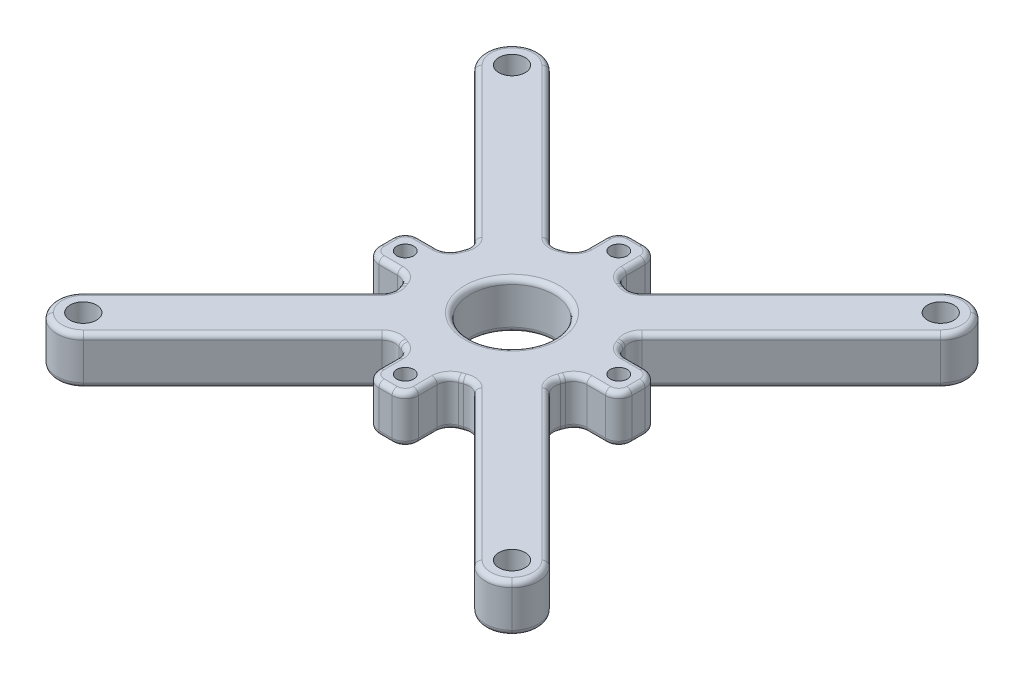
SolidWorks part; units mm, degrees
ref_plane "Front Plane" through (0, 0, 0) normal (0, 0, 1) x (1, 0, 0)
ref_plane "Top Plane" through (0, 0, 0) normal (0, 1, 0) x (1, 0, 0)
ref_plane "Right Plane" through (0, 0, 0) normal (1, 0, 0) x (0, 0, -1)
sketch "Geometry" plane through (0, 0, 0) normal (0, 1, 0) x (1, 0, 0)
  line L2 (-55, 0) -> (55, 0) construction
  line L3 (-24, -3.75) -> (24, -3.75) construction
  line L4 (-24, -3.75) -> (-24, 3.75) construction
  line L5 (-24, 3.75) -> (24, 3.75) construction
  line L6 (24, -3.75) -> (24, 3.75) construction
  line L7 (-24, -3.75) -> (24, 3.75) construction
  line L8 (-24, 3.75) -> (24, -3.75) construction
  line L9 (-3.75, -24) -> (3.75, -24) construction
  line L10 (-3.75, -24) -> (-3.75, 24) construction
  line L11 (-3.75, 24) -> (3.75, 24) construction
  line L12 (3.75, -24) -> (3.75, 24) construction
  line L13 (-3.75, -24) -> (3.75, 24) construction
  line L14 (-3.75, 24) -> (3.75, -24) construction
  line L15 (-16.0682, 3.75) -> (-24, 3.75)
  line L16 (-24, 3.75) -> (-24, -3.75)
  line L17 (-24, -3.75) -> (-16.0682, -3.75)
  line L18 (3.75, 16.0682) -> (3.75, 24)
  line L19 (3.75, 24) -> (-3.75, 24)
  line L20 (-3.75, 24) -> (-3.75, 16.0682)
  line L21 (16.0682, -3.75) -> (24, -3.75)
  line L22 (24, -3.75) -> (24, 3.75)
  line L23 (24, 3.75) -> (16.0682, 3.75)
  line L24 (-3.75, -16.0682) -> (-3.75, -24)
  line L25 (-3.75, -24) -> (3.75, -24)
  line L26 (3.75, -24) -> (3.75, -16.0682)
  circle A0 centre (0, 0) radius 7.9375
  circle A1 centre (0, 0) radius 16.5
  circle A2 centre (-20.25, 0) radius 1.6
  circle A3 centre (0, 20.25) radius 1.6
  circle A4 centre (20.25, 0) radius 1.6
  circle A5 centre (0, -20.25) radius 1.6
  circle A6 centre (-20.25, 0) radius 2.75
  circle A7 centre (0, 20.25) radius 2.75
  circle A8 centre (20.25, 0) radius 2.75
  circle A9 centre (0, -20.25) radius 2.75
  dimension "D1" = 15.875
  dimension "D2" = 33
  dimension "D6" = 3.2
  dimension "D8" = 5.5
  dimension "D3" = 7.5
  dimension "D4" = 24
  dimension "D5" = 3.75
  dimension "D7" = 4
  dimension "D9" = 4
  dimension "D10" = 4
extrude "Cap and Holes" add sketch "Geometry" along normal blind 9 contours A1 A0 | A1 L15 L16 L17 A6 | A1 L24 L25 L26 A9 | A1 L21 L22 L23 A8 | A1 L18 L19 L20 A7 | A7 A3 | A6 A2 | A9 A5 | A8 A4 region at (-16.6092, 0, 0) region at (-11.3373, 0, -11.3373) region at (-3.6408, 0, -20.0341) region at (0, 0, 16.6092) region at (20.0341, 0, -3.6408) region at (-22.9222, 0, 0) region at (-2.6722, 0, -20.25) region at (17.5778, 0, 0) region at (-2.6722, 0, 20.25)
extrude "Socket_Head" cut sketch "Sketch1<3>" along normal blind 3 contours A9 A5 | A8 A4 | A7 A3 | A6 A2 region at (-22.9222, 0, 0) region at (-2.6722, 0, -20.25) region at (17.5778, 0, 0) region at (-2.6722, 0, 20.25)
sketch "Sketch1<3>" plane through (0, 0, 0) normal (0, 1, 0) x (1, 0, 0) same geometry as "Geometry"
sketch "Sketch1" plane through (0, 9, 0) normal (0, 1, 0) x (1, 0, 0)
  line L0 (-47.7297, 40.6586) -> (40.6586, -47.7297)
  line L1 (40.6586, -47.7297) -> (47.7297, -40.6586)
  line L2 (47.7297, -40.6586) -> (-40.6586, 47.7297)
  line L3 (-40.6586, 47.7297) -> (-47.7297, 40.6586)
  line L4 (-44.1942, 44.1942) -> (44.1942, -44.1942) construction
  line L5 (-4.95, 0) -> (4.95, 0) construction
  line L6 (3.5355, 3.5355) -> (-3.5355, -3.5355) construction
  line L7 (0, -24) -> (0, 24) construction
  line L8 (3.75, 24) -> (-3.75, 24) construction
  line L9 (-47.7297, -40.6586) -> (40.6586, 47.7297)
  line L10 (-40.6586, -47.7297) -> (-47.7297, -40.6586)
  line L11 (47.7297, 40.6586) -> (-40.6586, -47.7297)
  line L12 (40.6586, 47.7297) -> (47.7297, 40.6586)
  line L13 (-44.1942, 37.1231) -> (-37.1231, 44.1942) construction
  circle A0 centre (-40.6586, 40.6586) radius 2.5
  circle A1 centre (40.6586, -40.6586) radius 2.5
  circle A2 centre (40.6586, 40.6586) radius 2.5
  circle A3 centre (-40.6586, -40.6586) radius 2.5
  point P10 (0, 0)
  point P11 (0, 0)
  point P14 (0, 0)
  point P20 (0, 0)
  point P29 (-40.6586, 40.6586)
  circle M15 centre (0, 0) radius 7.9375
  arc M16 (3.75, -16.0682) -> (16.0682, -3.75) centre (0, 0) ccw
  arc M20 (16.0682, 3.75) -> (3.75, 16.0682) centre (0, 0) ccw
  arc M24 (-3.75, 16.0682) -> (-16.0682, 3.75) centre (0, 0) ccw
  arc M28 (-16.0682, -3.75) -> (-3.75, -16.0682) centre (0, 0) ccw
  dimension "D4" = 5
  dimension "D1" = 45
  dimension "D2" = 125
  dimension "D3" = 10
  dimension "D5" = 5
extrude "Boss-Extrude1" add sketch "Sketch1" against normal up to surface (9 mm away) contours L2 L3 L0 A0 M24 | L12 L9 L11 A2 M20 | L1 L2 L0 A1 M16 | L11 L9 L10 A3 M28 | L2 L0 M15 M24 | L11 L9 M20 M15 | L2 L0 M16 M15 | L11 L9 M15 M28 region at (-27.2715, 9, -27.2715) region at (-8.3422, 9, -8.3422) region at (-8.3422, 9, 8.3422) region at (8.3422, 9, -8.3422) region at (-27.2715, 9, 27.2715) region at (8.3422, 9, 8.3422) region at (27.2715, 9, -27.2715) region at (27.2715, 9, 27.2715) up to face at (0, 0, 23)
fillet "Fillet1" radius 2.5 16 edges at (-16.0682, 4.5, -3.75) (-14.6542, 4.5, -7.5831) (-7.5831, 4.5, -14.6542) (-3.75, 4.5, -16.0682) (3.75, 4.5, -16.0682) (7.5831, 4.5, -14.6542) (16.0682, 4.5, -3.75) (14.6542, 4.5, -7.5831) (14.6542, 4.5, 7.5831) (16.0682, 4.5, 3.75) (3.75, 4.5, 16.0682) (7.5831, 4.5, 14.6542) (-3.75, 4.5, 16.0682) (-7.5831, 4.5, 14.6542) (-14.6542, 4.5, 7.5831) (-16.0682, 4.5, 3.75)
fillet "Fillet2" radius 2.5 8 edges at (-24, 4.5, 3.75) (-24, 4.5, -3.75) (-3.75, 4.5, -24) (3.75, 4.5, -24) (24, 4.5, -3.75) (24, 4.5, 3.75) (3.75, 4.5, 24) (-3.75, 4.5, 24)
fillet "Fillet3" radius 5 8 edges at (47.7297, 4.5, -40.6586) (40.6586, 4.5, -47.7297) (-40.6586, 4.5, -47.7297) (-47.7297, 4.5, -40.6586) (-47.7297, 4.5, 40.6586) (-40.6586, 4.5, 47.7297) (47.7297, 4.5, 40.6586) (40.6586, 4.5, 47.7297)
fillet "Fillet4" radius 1 120 edges at (-15.1986, 0, 7.5445) (-15.4573, 0, 5.7724) (-16.4945, 0, 4.2121) (-19.7213, 0, 3.75) (-23.2678, 0, 3.0178) (-24, 0, 0) (-23.2678, 0, -3.0178) (-19.7213, 0, -3.75) (-16.4945, 0, -4.2121) (-15.4573, 0, -5.7724) (-15.1986, 0, -7.5445) (-30.0369, 0, -22.9658) (-45.6586, 0, -40.6586) (-40.6586, 0, -45.6586) (-22.9658, 0, -30.0369) (-7.5445, 0, -15.1986) (-5.7724, 0, -15.4573) (-4.2121, 0, -16.4945) (-3.75, 0, -19.7213) (-3.0178, 0, -23.2678) (0, 0, -24) (3.0178, 0, -23.2678) (3.75, 0, -19.7213) (4.2121, 0, -16.4945) (5.7724, 0, -15.4573) (7.5445, 0, -15.1986) (22.9658, 0, -30.0369) (40.6586, 0, -45.6586) (45.6586, 0, -40.6586) (30.0369, 0, -22.9658) (15.1986, 0, -7.5445) (15.4573, 0, -5.7724) (16.4945, 0, -4.2121) (19.7213, 0, -3.75) (23.2678, 0, -3.0178) (24, 0, 0) (23.2678, 0, 3.0178) (19.7213, 0, 3.75) (16.4945, 0, 4.2121) (15.4573, 0, 5.7724) (15.1986, 0, 7.5445) (30.0369, 0, 22.9658) (45.6586, 0, 40.6586) (40.6586, 0, 45.6586) (22.9658, 0, 30.0369) (7.5445, 0, 15.1986) (5.7724, 0, 15.4573) (4.2121, 0, 16.4945) (3.75, 0, 19.7213) (3.0178, 0, 23.2678) (0, 0, 24) (-3.0178, 0, 23.2678) (-3.75, 0, 19.7213) (-4.2121, 0, 16.4945) (-5.7724, 0, 15.4573) (-7.5445, 0, 15.1986) (-22.9658, 0, 30.0369) (-40.6586, 0, 45.6586) (-45.6586, 0, 40.6586) (7.5445, 9, -15.1986) (5.7724, 9, -15.4573) (4.2121, 9, -16.4945) (3.75, 9, -19.7213) (3.0178, 9, -23.2678) (0, 9, -24) (-3.0178, 9, -23.2678) (-3.75, 9, -19.7213) (-4.2121, 9, -16.4945) (-5.7724, 9, -15.4573) (-7.5445, 9, -15.1986) (-22.9658, 9, -30.0369) (-40.6586, 9, -45.6586) (-45.6586, 9, -40.6586) (-30.0369, 9, -22.9658) (-15.1986, 9, -7.5445) (-15.4573, 9, -5.7724) (-16.4945, 9, -4.2121) (-19.7213, 9, -3.75) (-23.2678, 9, -3.0178) (-24, 9, 0) (-23.2678, 9, 3.0178) (-19.7213, 9, 3.75) (-16.4945, 9, 4.2121) (-15.4573, 9, 5.7724) (-15.1986, 9, 7.5445) (-30.0369, 9, 22.9658) (-45.6586, 9, 40.6586) (-40.6586, 9, 45.6586) (-22.9658, 9, 30.0369) (-7.5445, 9, 15.1986) (-5.7724, 9, 15.4573) (-4.2121, 9, 16.4945) (-3.75, 9, 19.7213) (-3.0178, 9, 23.2678) (0, 9, 24) (3.0178, 9, 23.2678) (3.75, 9, 19.7213) (4.2121, 9, 16.4945) (5.7724, 9, 15.4573) (7.5445, 9, 15.1986) (22.9658, 9, 30.0369) (40.6586, 9, 45.6586) (45.6586, 9, 40.6586) (30.0369, 9, 22.9658) (15.1986, 9, 7.5445) (15.4573, 9, 5.7724) (16.4945, 9, 4.2121) (19.7213, 9, 3.75) (23.2678, 9, 3.0178) (24, 9, 0) (23.2678, 9, -3.0178) (19.7213, 9, -3.75) (16.4945, 9, -4.2121) (15.4573, 9, -5.7724) (15.1986, 9, -7.5445) (30.0369, 9, -22.9658) (45.6586, 9, -40.6586) (40.6586, 9, -45.6586) (-30.0369, 0, 22.9658) (22.9658, 9, -30.0369)
fillet "Fillet5" radius 1 2 edges at (0, 9, 7.9375) (0, 0, 7.9375)
